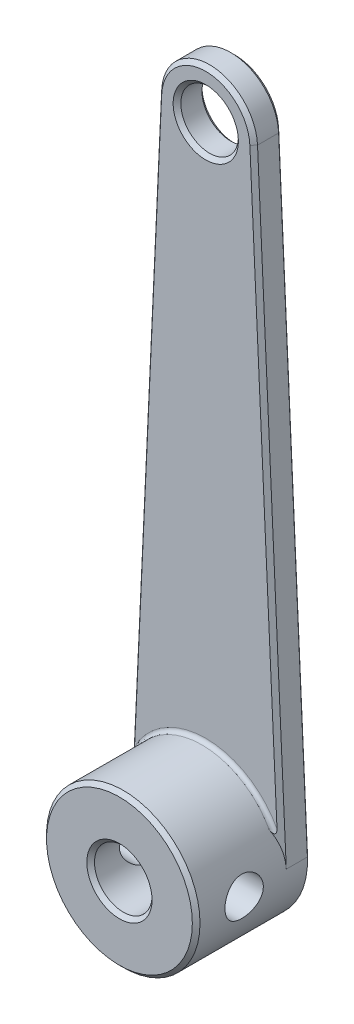
SolidWorks part; units mm, degrees
ref_plane "Front Plane" through (0, 0, 0) normal (0, 0, 1) x (1, 0, 0)
ref_plane "Top Plane" through (0, 0, 0) normal (0, 1, 0) x (1, 0, 0)
ref_plane "Right Plane" through (0, 0, 0) normal (1, 0, 0) x (0, 0, -1)
sketch "Sketch1" plane through (0, 0, 0) normal (0, 0, 1) x (1, 0, 0)
  circle A0 centre (0, 0) radius 4
  circle A1 centre (0, 0) radius 1.5
  dimension "D1" = 8
  dimension "D2" = 3
extrude "Boss-Extrude1" add sketch "Sketch1" along normal blind 6
sketch "Sketch2" plane through (0, 0, 0) normal (0, 0, 1) x (1, 0, 0)
  line L0 (-3.9956, 0.1875) -> (-2.4973, 32.1172)
  line L1 (0, 32) -> (0, 30.5) construction
  line L2 (3.9956, 0.1875) -> (2.4973, 32.1172)
  line L3 (0, 29.5) -> (0, 0) construction
  arc A0 (2.4973, 32.1172) -> (-2.4973, 32.1172) centre (0, 32) ccw
  circle A1 centre (0, 32) radius 1.5
  circle A2 centre (0, 0) radius 4 construction
  arc A3 (3.9956, 0.1875) -> (-3.9956, 0.1875) centre (0, 0) ccw
  dimension "D1" = 5
  dimension "D3" = 3
  dimension "D2" = 32
extrude "Boss-Extrude2" add sketch "Sketch2" along normal blind 1.5
sketch "Sketch3" plane through (0, 0, 0) normal (1, 0, 0) x (0, 0, -1)
  circle A0 centre (-3.5, 0) radius 1
  point P2 (0, 0)
  dimension "D1" = 2
  dimension "D2" = 3.5
extrude "Cut-Extrude1" cut sketch "Sketch3" against normal through all both and the other way through all
chamfer "Chamfer1" distance 0.2 angle 45 11 edges at (1.5, 32, 0) (1.5, 32, 1.5) (1.5, 0, 6) (4, 0, 6) (3.2464, 16.1523, 0) (0, 34.5, 0) (0, -4, 0) (-3.2464, 16.1523, 0) (3.2464, 16.1523, 1.5) (0, 34.5, 1.5) (-3.2464, 16.1523, 1.5)
fillet "Fillet1" radius 0.2 1 edges at (0, 4, 1.5)
